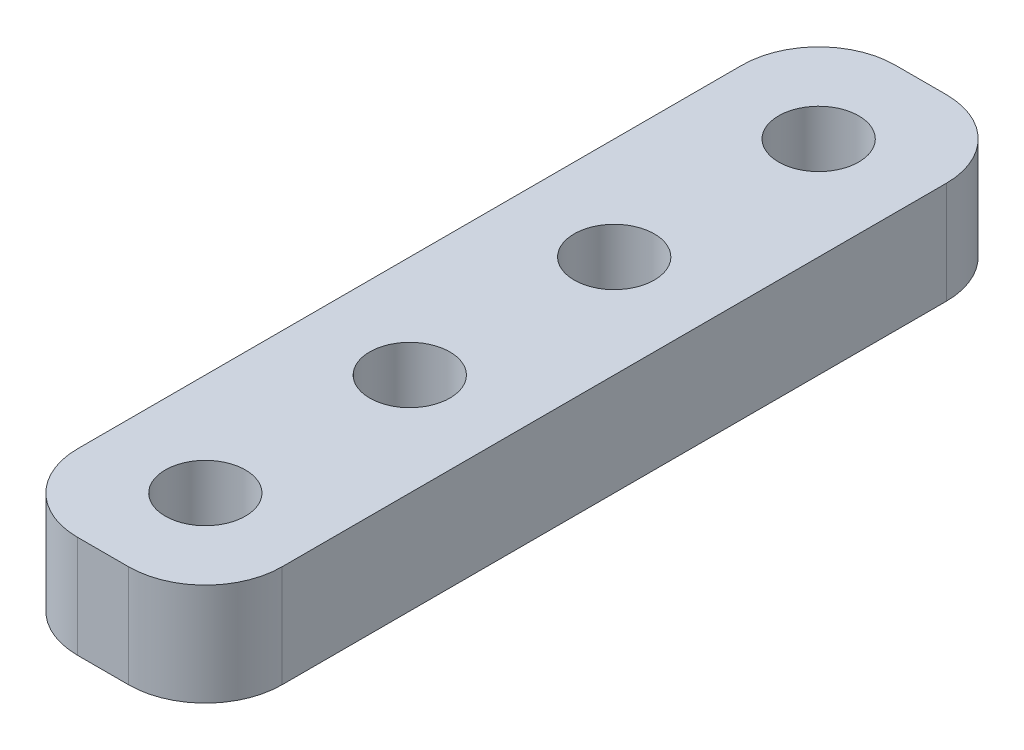
SolidWorks part; units mm, degrees
material "6061-T6 (SS)"
ref_plane "Front Plane" through (0, 0, 0) normal (0, 0, 1) x (1, 0, 0)
ref_plane "Top Plane" through (0, 0, 0) normal (0, 1, 0) x (1, 0, 0)
ref_plane "Right Plane" through (0, 0, 0) normal (1, 0, 0) x (0, 0, -1)
sketch "Sketch1" plane through (0, 0, 0) normal (0, 1, 0) x (1, 0, 0)
  line L0 (6.35, 0) -> (6.35, 50.8) construction
  line L1 (0, 0) -> (12.7, 0)
  line L2 (0, 0) -> (0, 50.8)
  line L3 (0, 50.8) -> (12.7, 50.8)
  line L4 (12.7, 0) -> (12.7, 50.8)
  circle A0 centre (6.35, 6.35) radius 2.4892
  point P9 (6.35, 5.8375)
  dimension "D3" = 4.9784
  dimension "D4" = 6.35
  dimension "D1" = 12.7
  dimension "D2" = 50.8
extrude "Boss-Extrude1" add sketch "Sketch1" along normal blind 6.35
pattern_linear "LPattern1" count 4 spacing 12.7 along (0, 0, -1) of face at (6.35, 6.35, -3.8608)
fillet "Fillet1" radius 4.7625 4 edges at (0, 3.175, -50.8) (12.7, 3.175, -50.8) (12.7, 3.175, 0) (0, 3.175, 0)
